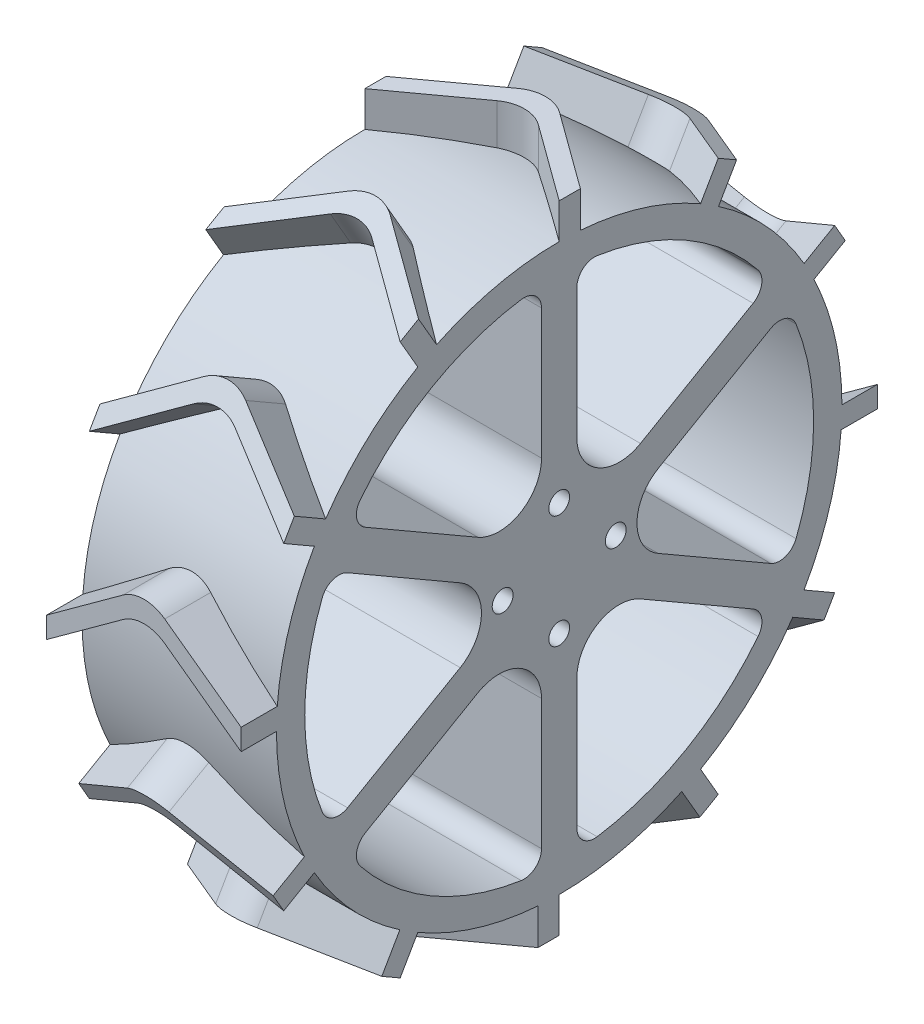
SolidWorks part; units mm, degrees
material "PLA 15%"
ref_plane "Front Plane" through (0, 0, 0) normal (0, 0, 1) x (1, 0, 0)
ref_plane "Top Plane" through (0, 0, 0) normal (0, 1, 0) x (1, 0, 0)
ref_plane "Right Plane" through (0, 0, 0) normal (1, 0, 0) x (0, 0, -1)
sketch "Sketch2" plane through (0, 0, 0) normal (1, 0, 0) x (0, 0, -1)
  circle A2 centre (0, 0) radius 40
  dimension "D1" = 80
extrude "Boss-Extrude1" add sketch "Sketch2" along normal blind 27.5
sketch "Sketch4" plane through (0, 0, 0) normal (0, 1, 0) x (1, 0, 0)
  line L8 (0, 0) -> (27.5, 0) construction
  line L9 (27.5, -40) -> (27.5, 40) construction
  line L10 (0, 0) -> (10.8091, 7.8612)
  line L11 (16.6909, 7.8612) -> (27.5, 0)
  line L12 (27.5, 0) -> (27.5, 3)
  line L13 (27.5, 3) -> (16.6909, 10.8612)
  line L14 (10.8091, 10.8612) -> (0, 3)
  line L15 (0, 40) -> (0, -40) construction
  line L16 (0, 3) -> (0, 0)
  arc A0 (16.6909, 10.8612) -> (10.8091, 10.8612) centre (13.75, 6.8175) ccw
  arc A1 (10.8091, 7.8612) -> (16.6909, 7.8612) centre (13.75, 3.8175) cw
  point P4 (13.75, 0)
  point P18 (13.75, 13)
  point P21 (13.75, 10)
  dimension "D3" = 5
  dimension "D1" = 3
  dimension "D2" = 3
  dimension "D4" = 10
extrude "Boss-Extrude2" add sketch "Sketch4" along normal blind 45
pattern_circular "CirPattern2" count 12 over 360 about axis through (27.5, 0, 0) along (-1, 0, 0) of "Boss-Extrude2"
sketch "Sketch5" plane through (0, 0, 0) normal (-1, 0, 0) x (0, 0, 1)
  line L0 (0, 0) -> (0, 40) construction
  line L1 (0, 0) -> (34.641, 20) construction
  line L6 (2.5, 33.1248) -> (2.5, 4.3301)
  line L8 (27.4369, 18.7274) -> (2.5, 4.3301)
  circle A0 centre (0, 0) radius 40 construction
  arc A2 (5.3731, 35.5968) -> (28.1411, 22.4517) centre (0, 0) cw
  arc A6 (28.1411, 22.4517) -> (27.4369, 18.7274) centre (26.1869, 20.8925) cw
  arc A7 (5.3731, 35.5968) -> (2.5, 33.1248) centre (5, 33.1248) ccw
  circle A10 centre (0, 0) radius 40 construction
  point P11 (0, 35.9131)
  point P22 (2.5, 35.9131)
  dimension "D1" = 2.5
  dimension "D2" = 4
  dimension "D8" = 2.5
  dimension "D7" = 2.5
  dimension "D9" = 60
extrude "Cut-Extrude3" cut sketch "Sketch5" against normal up to next
fillet "Fillet1" radius 6 1 edges at (13.75, 4.3301, 2.5)
pattern_circular "CirPattern3" count 6 over 360 about axis through (0, 0, 0) along (1, 0, 0) of "Cut-Extrude3", "Fillet1"
sketch "Sketch6" plane through (0, 0, 0) normal (-1, 0, 0) x (0, 0, 1)
  circle A0 centre (0, 8) radius 1.475
  circle A1 centre (8, 0) radius 1.475
  circle A2 centre (0, -8) radius 1.475
  circle A3 centre (-8, 0) radius 1.475
  point P0 (0, 0)
  point P13 (0, 0)
  dimension "D1" = 2.95
  dimension "D2" = 8
  dimension "D3" = 4
extrude "Cut-Extrude4" cut sketch "Sketch6" against normal up to next
sketch "Sketch7" plane through (0, 0, 0) normal (0, 1, 0) x (1, 0, 0)
